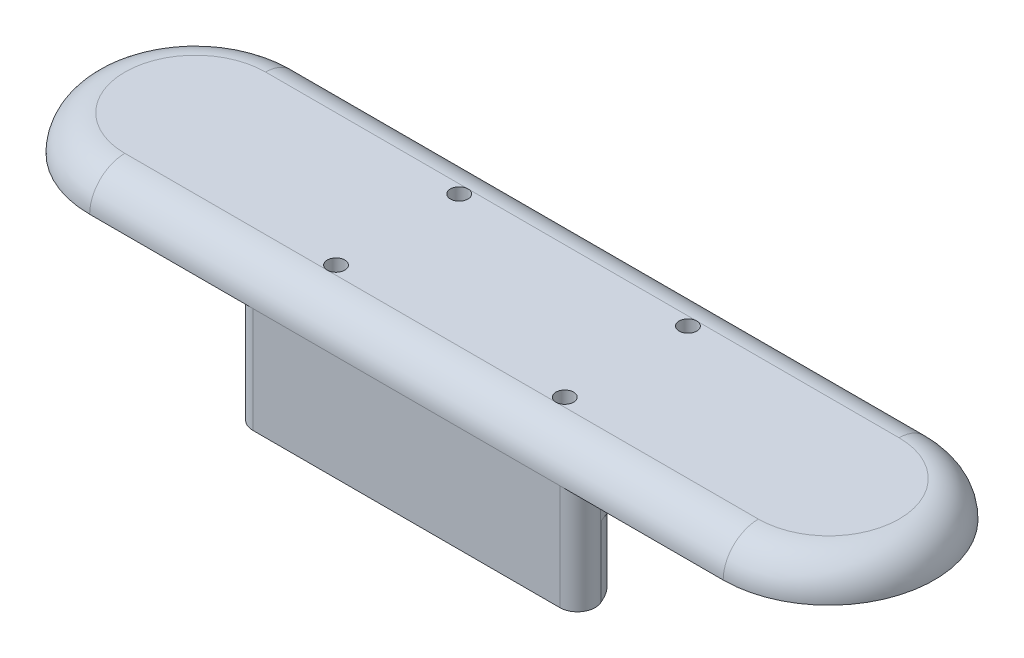
SolidWorks part; units mm, degrees
ref_plane "Front Plane" through (0, 0, 0) normal (0, 0, 1) x (1, 0, 0)
ref_plane "Top Plane" through (0, 0, 0) normal (0, 1, 0) x (1, 0, 0)
ref_plane "Right Plane" through (0, 0, 0) normal (1, 0, 0) x (0, 0, -1)
sketch "Sketch1" plane through (0, 0, 0) normal (0, 1, 0) x (1, 0, 0)
  line L0 (-67.6947, 31.5152) -> (112.3053, -28.4848) construction
  line L1 (-67.6947, 31.5152) -> (112.3053, 31.5152)
  line L3 (-67.6947, -28.4848) -> (112.3053, -28.4848)
  line L5 (112.3053, 31.5152) -> (-67.6947, -28.4848) construction
  line L6 (-67.6947, 31.5152) -> (-67.6947, -28.4848) construction
  arc A0 (-67.6947, 31.5152) -> (-67.6947, -28.4848) centre (-67.6947, 1.5152) ccw
  arc A1 (112.3053, 31.5152) -> (112.3053, -28.4848) centre (112.3053, 1.5152) cw
  point P6 (22.3053, 1.5152)
extrude "Boss-Extrude1" add sketch "Sketch1" along normal blind 40
fillet "Fillet1" radius 10 4 edges at (-97.6947, 40, -1.5152) (22.3053, 40, -31.5152) (142.3053, 40, -1.5152) (22.3053, 40, 28.4848)
sketch "Sketch3" plane through (0, 0, 0) normal (0, -1, 0) x (1, 0, 0)
  line L0 (112.3053, -31.5152) -> (-67.6947, -31.5152) construction
  line L5 (73.949, -31.5152) -> (148.949, -31.5152)
  line L6 (73.949, -31.5152) -> (73.949, 28.4848) construction
  line L7 (73.949, 28.4848) -> (148.949, 28.4848)
  line L8 (148.949, -31.5152) -> (148.949, 28.4848)
  line L9 (22.3053, 28.4848) -> (22.3053, -31.5152) construction
  line L10 (-67.6947, 28.4848) -> (112.3053, 28.4848) construction
  line L11 (-29.3384, -31.5152) -> (-29.3384, 28.4848) construction
  line L12 (-29.3384, 28.4848) -> (-104.3384, 28.4848)
  line L13 (-104.3384, -31.5152) -> (-104.3384, 28.4848)
  line L14 (-29.3384, -31.5152) -> (-104.3384, -31.5152)
  arc A2 (73.949, 28.4848) -> (73.949, -31.5152) centre (125.9106, -1.5152) ccw
  arc A3 (-29.3384, 28.4848) -> (-29.3384, -31.5152) centre (-81.3, -1.5152) cw
extrude "Cut-Extrude1" cut sketch "Sketch3" against normal blind 30
sketch "Sketch4" plane through (0, 30, 0) normal (0, -1, 0) x (-1, 0, 0)
  line L0 (67.6947, -28.4848) -> (67.6947, 31.5152) construction
  line L1 (-112.3053, -28.4848) -> (-112.3053, 31.5152) construction
  circle A0 centre (-112.3053, 1.5152) radius 5
  circle A1 centre (67.6947, 1.5152) radius 5
extrude "Boss-Extrude3" add sketch "Sketch4" along normal blind 10
ref_plane "Plane1" through (73.949, 0, 0) normal (1, 0, 0) x (0, 0, -1)
sketch "Sketch5" plane through (73.949, 0, 0) normal (1, 0, 0) x (0, 0, -1)
  line L0 (-28.4848, 0) -> (31.5152, 0) construction
  line L1 (11.5152, 20) -> (-8.4848, 20)
  line L2 (11.5152, 20) -> (11.5152, -20)
  line L3 (11.5152, -20) -> (-8.4848, -20)
  line L4 (-8.4848, 20) -> (-8.4848, -20)
  line L5 (11.5152, 20) -> (-8.4848, -20) construction
  line L6 (11.5152, -20) -> (-8.4848, 20) construction
  point P0 (1.5152, 0)
extrude "Cut-Extrude2" cut sketch "Sketch5" against normal up to next
fillet "Fillet2" radius 5 4 edges at (73.949, 15, 28.4848) (73.949, 15, -31.5152) (-29.3384, 15, -31.5152) (-29.3384, 15, 28.4848)
sketch "Sketch6" plane through (0, 0, 0) normal (0, -1, 0) x (-1, 0, 0)
  line L0 (-22.3053, -28.4848) -> (-22.3053, 31.5152) construction
  line L1 (21.3, -28.4848) -> (-65.9106, -28.4848) construction
  line L2 (-65.9106, 31.5152) -> (21.3, 31.5152) construction
  line L4 (10.1947, -15.9848) -> (-54.8053, -15.9848) construction
  line L5 (10.1947, -15.9848) -> (10.1947, 19.0152) construction
  line L6 (10.1947, 19.0152) -> (-54.8053, 19.0152) construction
  line L7 (-54.8053, -15.9848) -> (-54.8053, 19.0152) construction
  line L8 (10.1947, -15.9848) -> (-54.8053, 19.0152) construction
  line L9 (10.1947, 19.0152) -> (-54.8053, -15.9848) construction
  circle A0 centre (10.1947, -15.9848) radius 1
  circle A1 centre (-54.8053, -15.9848) radius 1
  circle A2 centre (-54.8053, 19.0152) radius 1
  circle A3 centre (10.1947, 19.0152) radius 1
  point P6 (-22.3053, 1.5152)
extrude "Cut-Extrude3" cut sketch "Sketch6" against normal up to next
sketch "Sketch7" plane through (0, 40, 0) normal (0, 1, 0) x (1, 0, 0)
  circle A0 centre (-10.1947, 19.0152) radius 2.5
  circle A1 centre (-10.1947, -15.9848) radius 2.5
  circle A2 centre (54.8053, -15.9848) radius 2.5
  circle A3 centre (54.8053, 19.0152) radius 2.5
extrude "Cut-Extrude4" cut sketch "Sketch7" against normal blind 5
sketch "Sketch8" plane through (0, 0, 0) normal (0, -1, 0) x (1, 0, 0)
  circle A0 centre (-22.1392, 8.4848) radius 6
  circle A1 centre (-22.1392, -11.5152) radius 6
  circle A2 centre (66.7498, -11.5152) radius 6
  circle A3 centre (66.7498, 8.4848) radius 6
extrude "Cut-Extrude5" cut sketch "Sketch8" against normal up to vertex (20 mm away) up to point (-22.1392, 20, 8.4848)
fillet "Fillet3" radius 15 8 edges at (60.7498, 10, -11.5152) (68.0443, 10, -17.3738) (60.7498, 10, 8.4848) (68.0443, 10, 14.3435) (-23.4337, 10, -17.3738) (-16.1392, 10, -11.5152) (-16.1392, 10, 8.4848) (-23.4337, 10, 14.3435)
